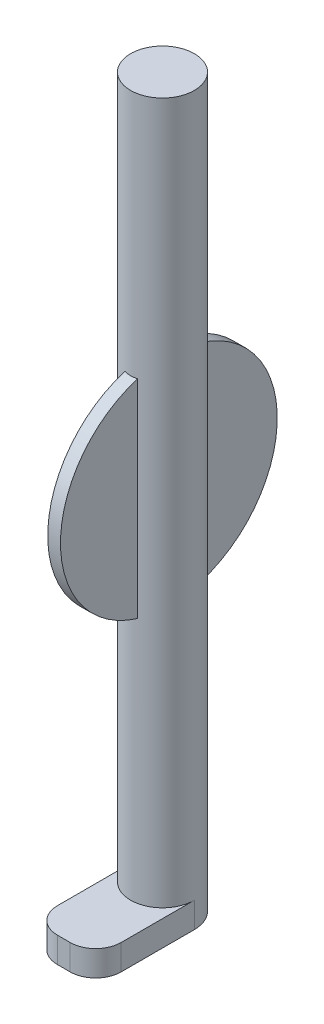
SolidWorks part; units mm, degrees
ref_plane "Front Plane" through (0, 0, 0) normal (0, 0, 1) x (1, 0, 0)
ref_plane "Top Plane" through (0, 0, 0) normal (0, 1, 0) x (1, 0, 0)
ref_plane "Right Plane" through (0, 0, 0) normal (1, 0, 0) x (0, 0, -1)
sketch "Sketch1" plane through (0, 0, 0) normal (0, 1, 0) x (1, 0, 0)
  circle A0 centre (0, 0) radius 2.5
extrude "Boss-Extrude1" add sketch "Sketch1" along normal blind 55
sketch "Sketch2" plane through (0, 0, 0) normal (1, 0, 0) x (0, 0, -1)
  line L0 (0, 0) -> (0, 55) construction
  line L1 (2.5, 55) -> (-2.5, 55) construction
  circle A0 centre (0, 27.5) radius 8.5
  dimension "D1" = 17
extrude "Boss-Extrude2" add sketch "Sketch2" along normal blind 0.5 and the other way blind 0.5
sketch "Sketch3" plane through (0, 0, 0) normal (0, -1, 0) x (1, 0, 0)
  line L2 (-2.5, 0) -> (-2.5, 7.7426)
  line L3 (-2.5, 7.7426) -> (2.5, 7.7426)
  line L4 (2.5, 0) -> (2.5, 7.7426)
  circle A0 centre (0, 0) radius 2.5 construction
  circle A2 centre (0, 0) radius 2.5
  arc A3 (-2.5, 0) -> (2.5, 0) centre (0, 0) ccw
  dimension "D1" = 0
extrude "Boss-Extrude3" add sketch "Sketch3" along normal blind 2
fillet "Fillet1" radius 2 2 edges at (-2.5, -1, 7.7426) (2.5, -1, 7.7426)
